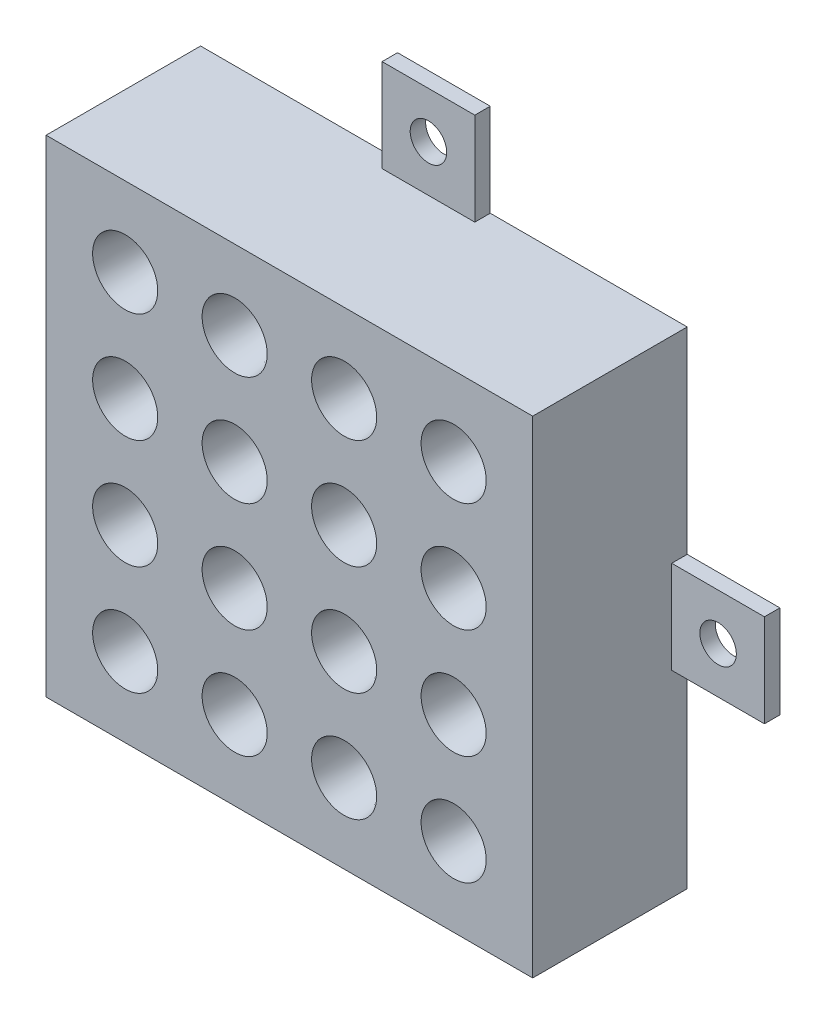
SolidWorks part; units mm, degrees
ref_plane "Front Plane" through (0, 0, 0) normal (0, 0, 1) x (1, 0, 0)
ref_plane "Top Plane" through (0, 0, 0) normal (0, 1, 0) x (1, 0, 0)
ref_plane "Right Plane" through (0, 0, 0) normal (1, 0, 0) x (0, 0, -1)
sketch "Sketch1" plane through (0, 0, 0) normal (0, 0, 1) x (1, 0, 0)
  line L1 (-52.4737, 14.5622) -> (-12.4737, 14.5622)
  line L2 (-52.4737, 14.5622) -> (-52.4737, -25.4378)
  line L3 (-52.4737, -25.4378) -> (-12.4737, -25.4378)
  line L4 (-12.4737, 14.5622) -> (-12.4737, -25.4378)
  dimension "D1" = 40
  dimension "D2" = 40
extrude "Boss-Extrude1" add sketch "Sketch1" along normal blind 12.7
sketch "Sketch2" plane through (0, 0, 12.7) normal (0, 0, 1) x (1, 0, 0)
  line L0 (-12.4737, 14.5622) -> (-52.4737, 14.5622) construction
  line L1 (-52.4737, 14.5622) -> (-52.4737, -25.4378) construction
  circle A0 centre (-45.9737, 8.0622) radius 2.6756
  circle A1 centre (-36.9737, 8.0622) radius 2.6756
  circle A2 centre (-27.9737, 8.0622) radius 2.6756
  circle A3 centre (-18.9737, 8.0622) radius 2.6756
  circle A4 centre (-45.9737, -0.9378) radius 2.6756
  circle A5 centre (-36.9737, -0.9378) radius 2.6756
  circle A6 centre (-27.9737, -0.9378) radius 2.6756
  circle A7 centre (-18.9737, -0.9378) radius 2.6756
  circle A8 centre (-45.9737, -9.9378) radius 2.6756
  circle A9 centre (-36.9737, -9.9378) radius 2.6756
  circle A10 centre (-27.9737, -9.9378) radius 2.6756
  circle A11 centre (-18.9737, -9.9378) radius 2.6756
  circle A12 centre (-45.9737, -18.9378) radius 2.6756
  circle A13 centre (-36.9737, -18.9378) radius 2.6756
  circle A14 centre (-27.9737, -18.9378) radius 2.6756
  circle A15 centre (-18.9737, -18.9378) radius 2.6756
  dimension "D1" = 5.3512
  dimension "D2" = 6.5
  dimension "D5" = 6.5
  dimension "D6" = 9
  dimension "D3" = 4
  dimension "D4" = 4
extrude "Cut-Extrude1" cut sketch "Sketch2" against normal blind 11.176 draft 8.75
sketch "Sketch3" plane through (0, 14.5622, 0) normal (0, 1, 0) x (1, 0, 0)
  line L0 (-12.4737, 0) -> (-52.4737, 0) construction
  line L1 (-36.2837, 0) -> (-28.6637, 0)
  line L2 (-36.2837, 0) -> (-36.2837, -1.27)
  line L3 (-36.2837, -1.27) -> (-28.6637, -1.27)
  line L4 (-28.6637, 0) -> (-28.6637, -1.27)
  line L7 (-12.4737, -12.7) -> (-12.4737, 0) construction
  dimension "D1" = 1.27
  dimension "D2" = 7.62
  dimension "D3" = 16.19
extrude "Boss-Extrude2" add sketch "Sketch3" along normal blind 7.62
sketch "Sketch4" plane through (-12.4737, 0, 0) normal (1, 0, 0) x (0, 0, -1)
  line L0 (0, -25.4378) -> (0, 14.5622) construction
  line L1 (-1.27, -1.6278) -> (0, -1.6278)
  line L2 (-1.27, -1.6278) -> (-1.27, -9.2478)
  line L3 (-1.27, -9.2478) -> (0, -9.2478)
  line L4 (0, -1.6278) -> (0, -9.2478)
  dimension "D1" = 7.62
  dimension "D2" = 16.19
  dimension "D3" = 1.27
extrude "Boss-Extrude3" add sketch "Sketch4" along normal blind 7.62
sketch "Sketch5" plane through (-52.4737, 0, 0) normal (-1, 0, 0) x (0, 0, 1)
  line L0 (0, 14.5622) -> (0, -25.4378) construction
  line L1 (1.27, -1.6277) -> (0, -1.6277)
  line L2 (1.27, -1.6277) -> (1.27, -9.2477)
  line L3 (1.27, -9.2477) -> (0, -9.2477)
  line L4 (0, -1.6277) -> (0, -9.2477)
  dimension "D1" = 16.19
  dimension "D2" = 7.62
  dimension "D3" = 1.27
extrude "Boss-Extrude4" add sketch "Sketch5" along normal blind 7.62
sketch "Sketch6" plane through (0, -25.4378, 0) normal (0, -1, 0) x (1, 0, 0)
  line L0 (-52.4737, 0) -> (-12.4737, 0) construction
  line L1 (-36.2838, 1.27) -> (-28.6638, 1.27)
  line L2 (-36.2838, 1.27) -> (-36.2838, 0)
  line L3 (-36.2838, 0) -> (-28.6638, 0)
  line L4 (-28.6638, 1.27) -> (-28.6638, 0)
  dimension "D1" = 7.62
  dimension "D2" = 16.19
  dimension "D3" = 1.27
extrude "Boss-Extrude5" add sketch "Sketch6" along normal blind 7.62
sketch "Sketch7" plane through (0, 0, 1.27) normal (0, 0, 1) x (1, 0, 0)
  line L0 (-28.6638, -33.0578) -> (-28.6638, -25.4378) construction
  line L1 (-28.6638, -33.0578) -> (-36.2838, -33.0578) construction
  line L2 (-60.0937, -9.2477) -> (-52.4737, -9.2477) construction
  line L3 (-60.0937, -9.2477) -> (-60.0937, -1.6277) construction
  line L4 (-4.8537, -9.2478) -> (-12.4737, -9.2478) construction
  line L5 (-4.8537, -1.6278) -> (-4.8537, -9.2478) construction
  line L6 (-36.2837, 22.1822) -> (-28.6637, 22.1822) construction
  line L7 (-28.6637, 22.1822) -> (-28.6637, 14.5622) construction
  circle A0 centre (-32.4738, -29.2478) radius 1.5
  circle A1 centre (-56.2837, -5.4377) radius 1.5
  circle A2 centre (-8.6637, -5.4378) radius 1.5
  circle A3 centre (-32.4737, 18.3722) radius 1.5
  dimension "D1" = 3
  dimension "D4" = 3
  dimension "D7" = 3
  dimension "D10" = 3.81
  dimension "D12" = 3
  dimension "D2" = 3.81
  dimension "D3" = 3.81
  dimension "D5" = 3.81
  dimension "D6" = 3.81
  dimension "D8" = 3.81
  dimension "D9" = 3.81
  dimension "D11" = 3.81
  dimension "D13" = 47.62
  dimension "D14" = 47.62
extrude "M3 diameter holes" cut sketch "Sketch7" against normal blind 7.62 contours A0 | A2 | A1 | A3
sketch "Sketch8" plane through (0, -25.4378, 0) normal (0, -1, 0) x (1, 0, 0)
  line L2 (-28.6638, 0) -> (-12.4737, 0) construction
  line L4 (-52.4737, 12.7) -> (-52.4737, 0) construction
  circle A0 centre (-32.4737, 5.08) radius 0.4572
  circle A1 centre (-32.4737, 5.08) radius 0.0267
  dimension "D1" = 0.9144
  dimension "D4" = 0.0533
  dimension "D2" = 5.08
  dimension "D3" = 20
ref_axis "Axis1" through (-32.4737, -25.4378, 5.08) along (0, -1, 0)
ref_plane "Plane1" through (-32.4737, 0, 0) normal (1, 0, 0) x (0, 0, -1)
sketch "Sketch10" plane through (-32.4737, 0, 0) normal (1, 0, 0) x (0, 0, -1)
  line L0 (-5.08, -25.4378) -> (-7.1218, -17.8178)
  line L1 (-5.5372, -25.4378) -> (-4.6228, -25.4378) construction
  line L2 (0, -25.4378) -> (0, -9.2478) construction
  dimension "D1" = 7.62
  dimension "D2" = 15
ref_plane "Plane3" through (-32.4737, -25.4378, 5.08) normal (0, 0.9659, 0.2588) x (-1, 0, 0)
hole_wizard "#64 (0.036) Diameter Hole1" positions "Sketch16" profile "Sketch15" hole size "#64" standard "Ansi Inch"
sketch "Sketch16" plane through (-32.4737, -25.4378, 5.08) normal (0, 0.9659, 0.2588) x (-1, 0, 0)
  point P0 (0, 0)
  dimension "D1" = 0
sketch "Sketch15" plane through (-32.4737, -25.4378, 5.08) normal (1, 0, 0) x (0, 0.2588, -0.9659)
  line L0 (0, 0) -> (0, 7.8747)
  line L1 (0, 7.8747) -> (0.4572, 7.6)
  line L2 (0.4572, 7.6) -> (0.4572, 0)
  line L5 (0.4572, 0) -> (0, 0)
  line L10 (0, 7.8747) -> (-0.4572, 7.6) construction
  line L11 (0, -6.35) -> (0, 107.95) construction
  dimension "Hole Dia." = 0.9144
  dimension "Hole Depth" = 7.6
  dimension "Drill Angle" = 118
extrude "Cut-Extrude3" cut sketch "Sketch8" along direction (0, 0.9659, 0.2588) on the side against the normal blind 2
equation "\"D3@Sketch8\" = \"D1@Sketch1\"/2"
